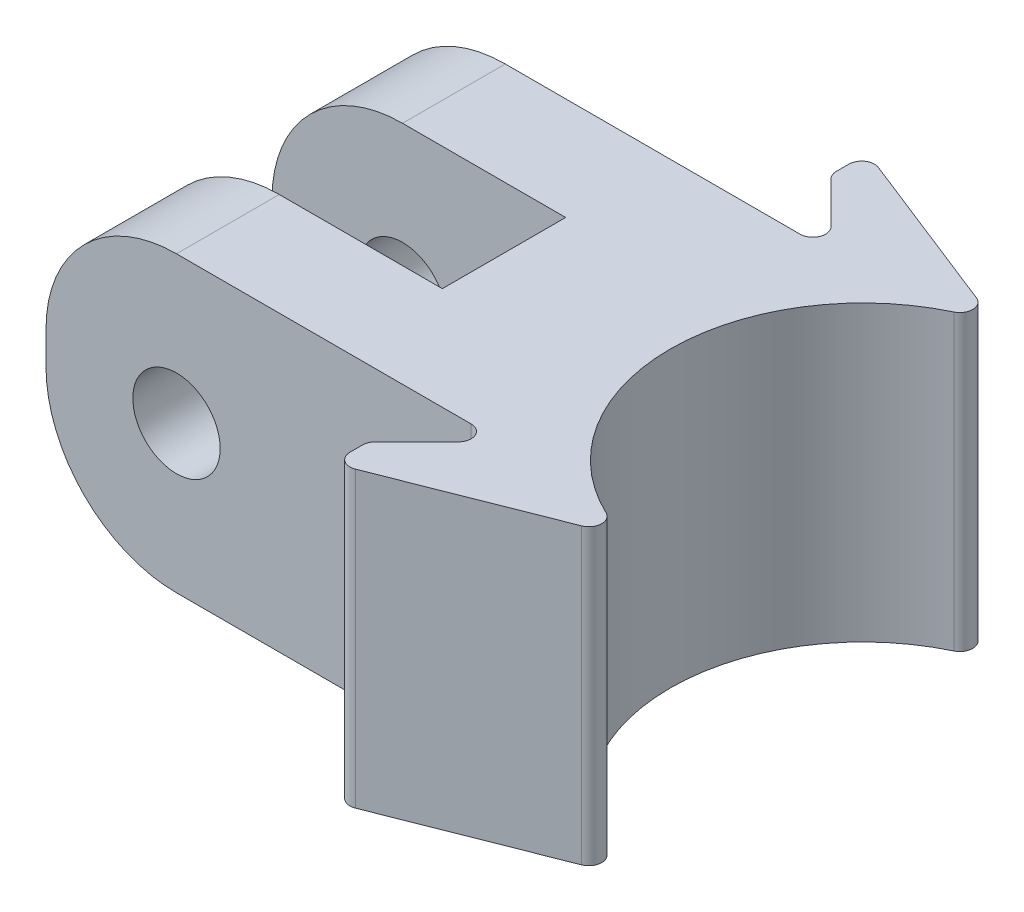
SolidWorks part; units mm, degrees
ref_plane "Front Plane" through (0, 0, 0) normal (0, 0, 1) x (1, 0, 0)
ref_plane "Top Plane" through (0, 0, 0) normal (0, 1, 0) x (1, 0, 0)
ref_plane "Right Plane" through (0, 0, 0) normal (1, 0, 0) x (0, 0, -1)
sketch "Sketch1" plane through (0, 0, 0) normal (0, 1, 0) x (1, 0, 0)
  line L0 (-158.9383, 0) -> (7787.9768, 0) construction
  line L1 (-11.43, 2.4) -> (0, 2.4)
  line L2 (0, 2.4) -> (0, -2.4)
  line L3 (0, -2.4) -> (-11.43, -2.4)
  line L4 (-11.43, 2.4) -> (-11.43, 6.4)
  line L5 (-11.43, 6.4) -> (6.3299, 6.4)
  line L6 (13.97, 6.4) -> (13.97, -6.4)
  line L7 (6.3299, -6.4) -> (-11.43, -6.4)
  line L8 (-11.43, -6.4) -> (-11.43, -2.4)
  line L9 (6.3299, 6.4) -> (3.7148, 9.0151)
  line L10 (3.7148, 9.0151) -> (3.7148, 10.444)
  line L11 (3.7148, 10.444) -> (13.97, 6.4)
  line L12 (3.7148, -10.444) -> (13.97, -6.4)
  line L13 (6.3299, -6.4) -> (3.7148, -9.0151)
  line L14 (3.7148, -9.0151) -> (3.7148, -10.444)
  point P5 (0, 0)
  dimension "D1" = 4.8
  dimension "D2" = 11.43
  dimension "D3" = 4
  dimension "D4" = 25.4
extrude "Boss-Extrude1" add sketch "Sketch1" along normal blind 11.43
fillet "Fillet1" radius 5.08 4 edges at (-11.43, 0, 4.4) (-11.43, 0, -4.4) (-11.43, 11.43, 4.4) (-11.43, 11.43, -4.4)
sketch "Sketch2" plane through (0, 0, 6.4) normal (0, 0, 1) x (1, 0, 0)
  line L0 (-6.35, 11.43) -> (-6.35, 0) construction
  point P6 (-6.35, 5.715)
hole_wizard "M3 Clearance Hole1" positions "Sketch3" profile "Sketch4" hole size "M3" standard "ANSI Metric" end condition through all
sketch "Sketch3" plane through (0, 0, 6.4) normal (0, 0, 1) x (1, 0, 0)
  point P0 (-6.35, 5.715)
sketch "Sketch4" plane through (-6.35, 5.715, 6.4) normal (1, 0, 0) x (0, -1, 0)
  line L0 (0, 0) -> (0, 16.844)
  line L1 (0, 16.844) -> (1.7, 16.844)
  line L2 (1.7, 16.844) -> (1.7, 0)
  line L5 (1.7, 0) -> (0, 0)
  line L11 (0, -6.35) -> (0, 107.95) construction
  dimension "Thru Hole Dia." = 3.4
  dimension "Thru Hole Depth" = 16.844
sketch "Sketch5" plane through (0, 11.43, 0) normal (0, 1, 0) x (1, 0, 0)
  line L0 (13.97, -6.4) -> (13.97, 6.4) construction
  circle A0 centre (13.97, 0) radius 7.5
  dimension "D1" = 15
extrude "Cut-Extrude1" cut sketch "Sketch5" against normal through all both and the other way through all contours A0
fillet "Fillet2" radius 0.5 8 edges at (3.7148, 5.715, 10.444) (3.7148, 5.715, 9.0151) (6.3299, 5.715, 6.4) (6.3299, 5.715, -6.4) (3.7148, 5.715, -9.0151) (3.7148, 5.715, -10.444) (11.9112, 5.715, 7.2119) (11.9112, 5.715, -7.2119)
